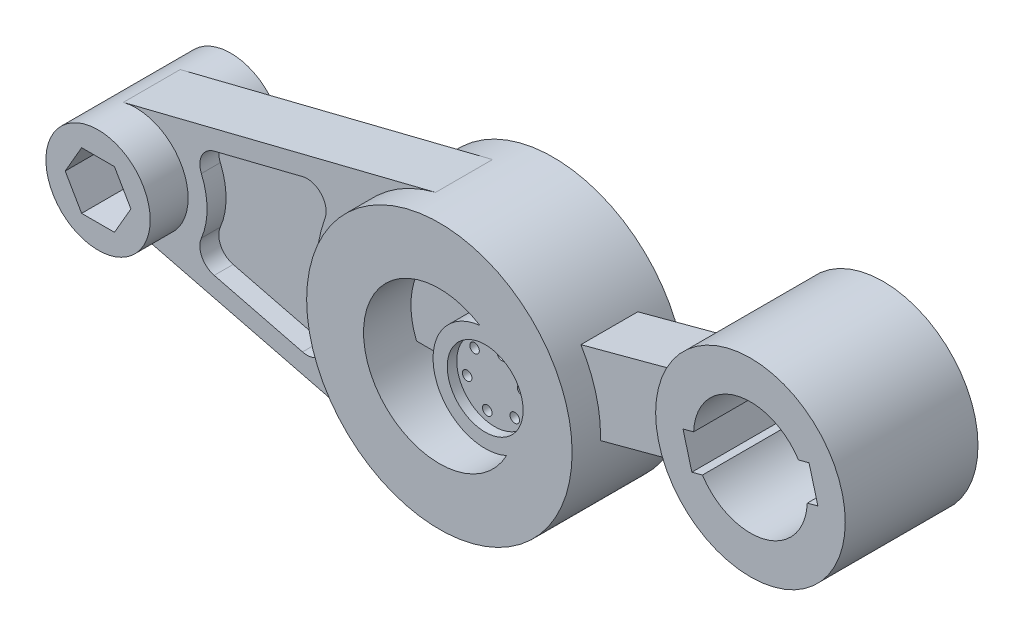
SolidWorks part; units mm, degrees
material "Copper"
ref_plane "Front Plane" through (0, 0, 0) normal (0, 0, 1) x (1, 0, 0)
ref_plane "Top Plane" through (0, 0, 0) normal (0, 1, 0) x (1, 0, 0)
ref_plane "Right Plane" through (0, 0, 0) normal (1, 0, 0) x (0, 0, -1)
ref_plane "CENTRE_Plane" through (175, 0, 0) normal (1, 0, 0) x (0, 0, -1)
ref_axis "CENTRE_Plane_Axis" through (175, 0, 33) along (0, 0, -1)
ref_plane "CENTRE_RIGHT_Plane" through (163.2772, 43.75, 0) normal (0.9659, 0.2588, 0) x (0, 0, -1)
ref_plane "RIGHT_Plane" through (332.3142, 89.0433, 0) normal (0.9659, 0.2588, 0) x (0, 0, -1)
sketch "Sketch1" plane through (0, 0, 0) normal (0, 0, 1) x (1, 0, 0)
  line L0 (-6.6786, 26.6767) -> (158, 67.9043)
  line L1 (-6.6786, -26.6767) -> (158, -67.9043)
  arc A0 (-6.6786, 26.6767) -> (-6.6786, -26.6767) centre (0, 0) ccw
  arc A1 (158, -67.9043) -> (158, 67.9043) centre (175, 0) ccw
  dimension "D1" = 55
  dimension "D2" = 140
extrude "LEFT_ARM" add sketch "Sketch1" along normal mid plane 30
sketch "Sketch2" plane through (0, 0, 0) normal (0, 0, 1) x (1, 0, 0)
  circle A0 centre (0, 0) radius 27.5
  dimension "D1" = 55
extrude "LEFT_Boss" add sketch "Sketch2" along normal mid plane 70
sketch "Sketch4" plane through (0, 0, 35) normal (0, 0, 1) x (1, 0, 0)
  line L0 (33, 0) -> (-33, 0) construction
  line L1 (17.3205, 0) -> (8.6603, 15)
  line L2 (8.6603, 15) -> (-8.6603, 15)
  line L3 (-8.6603, 15) -> (-17.3205, 0)
  line L4 (-17.3205, 0) -> (-8.6603, -15)
  line L5 (-8.6603, -15) -> (8.6603, -15)
  line L6 (8.6603, -15) -> (17.3205, 0)
  circle A0 centre (0, 0) radius 15 construction
  dimension "D1" = 30
extrude "LEFT_Hex" cut sketch "Sketch4" against normal through all both and the other way through all
sketch "Sketch3" plane through (0, 0, 0) normal (0, 0, 1) x (1, 0, 0)
  circle A0 centre (175, 0) radius 70
  dimension "D1" = 140
extrude "CENTRE_Boss" add sketch "Sketch3" along normal mid plane 60
sketch "Sketch5" plane through (163.2772, 43.75, 0) normal (0.9659, 0.2588, 0) x (0, 0, -1)
  line L0 (-33, -45.2933) -> (33, -45.2933) construction
  line L1 (-15, -65.2933) -> (15, -65.2933)
  line L2 (-15, -65.2933) -> (-15, -25.2933)
  line L3 (-15, -25.2933) -> (15, -25.2933)
  line L4 (15, -65.2933) -> (15, -25.2933)
  line L5 (-15, -65.2933) -> (15, -25.2933) construction
  line L6 (-15, -25.2933) -> (15, -65.2933) construction
  line L7 (0, 55) -> (0, -55) construction
  point P0 (0, -45.2933)
  dimension "D1" = 30
  dimension "D2" = 40
extrude "RIGHT_ARM" add sketch "Sketch5" along normal up to surface (175 mm away) up to plane "RIGHT_Plane"
sketch "RIGHT_ARM_CL" plane through (0, 0, 0) normal (0, 0, 1) x (1, 0, 0)
  line L0 (175, 0) -> (344.037, 45.2933) construction
  line L1 (347.6206, 31.9192) -> (317.0079, 146.1675) construction
sketch "Sketch7" plane through (0, 0, 0) normal (0, 0, 1) x (1, 0, 0)
  circle A0 centre (344.037, 45.2933) radius 50
  dimension "D1" = 100
extrude "RIGHT_Boss" add sketch "Sketch7" along normal mid plane 70
sketch "Sketch8" plane through (0, 0, 35) normal (0, 0, 1) x (1, 0, 0)
  circle A0 centre (344.037, 45.2933) radius 30
  dimension "D1" = 60
extrude "RIGHT_Boss_Hole" cut sketch "Sketch8" against normal through all
sketch "Sketch9" plane through (0, 0, 30) normal (0, 0, 1) x (1, 0, 0)
  circle A0 centre (175, 0) radius 40
  dimension "D1" = 80
extrude "CENTRE_Hole" cut sketch "Sketch9" against normal through all
sketch "Sketch10" plane through (0, 0, 0) normal (0, 0, 1) x (1, 0, 0)
  line L0 (175, 0) -> (344.037, 45.2933) construction
  line L1 (178.9358, -14.6885) -> (147.6187, 102.1885) construction
  circle A0 centre (199.1481, 6.4705) radius 27.5
  dimension "D1" = 55
  dimension "D2" = 25
extrude "CENTRE_Blob" add sketch "Sketch10" along normal mid plane 60
sketch "Sketch11" plane through (175, 0, 0) normal (1, 0, 0) x (0, 0, -1)
  line L1 (-5, -15) -> (5, -15)
  line L2 (-5, -15) -> (-5, 15)
  line L3 (-5, 15) -> (5, 15)
  line L4 (5, -15) -> (5, 15)
  line L5 (-5, -15) -> (5, 15) construction
  line L6 (-5, 15) -> (5, -15) construction
  point P0 (0, 0)
  dimension "D1" = 10
  dimension "D2" = 30
extrude "CENTRE_Beam" add sketch "Sketch11" along normal up to next and the other way up to next
sketch "Sketch12" plane through (0, 0, 30) normal (0, 0, 1) x (1, 0, 0)
  circle A0 centre (199.1481, 6.4705) radius 20
  dimension "D1" = 40
extrude "Cut-Extrude4" cut sketch "Sketch12" against normal blind 5
hole_wizard "M6x1.0 Tapped Hole1" positions "Sketch13" profile "Sketch14" tap size "M6x1.0" standard "ANSI Metric" end condition up to next
sketch "Sketch13" plane through (0, 0, 25) normal (0, 0, 1) x (1, 0, 0)
  line L0 (175, 0) -> (344.037, 45.2933) construction
  circle A0 centre (199.1481, 6.4705) radius 20 construction
  point P0 (184.6593, 2.5882)
  dimension "D1" = 15
sketch "Sketch14" plane through (184.6593, 2.5882, 25) normal (1, 0, 0) x (0, -1, 0)
  line L0 (0, 0) -> (0, 55)
  line L1 (0, 55) -> (2.5, 55)
  line L2 (2.5, 55) -> (2.5, 0)
  line L5 (2.5, 0) -> (0, 0)
  line L11 (0, -6.35) -> (0, 107.95) construction
  dimension "Thru Tap Drill Dia." = 5
  dimension "Thru Tap Drill Depth" = 55
cosmetic thread "Hole Thread1" parameters "D2"=6
pattern_circular "CirPattern1" count 6 over 360 about axis through (199.1481, 6.4705, 25) along (0, 0, 1) of "M6x1.0 Tapped Hole1"
cosmetic thread "Hole Thread2" parameters "D2"=6
cosmetic thread "Hole Thread3" parameters "D2"=6
cosmetic thread "Hole Thread4" parameters "D2"=6
cosmetic thread "Hole Thread5" parameters "D2"=6
cosmetic thread "Hole Thread6" parameters "D2"=6
cosmetic thread "Hole Thread7" parameters "D2"=6
cosmetic thread "Hole Thread8" parameters "D2"=6
mirror "Mirror1" about plane through (0, 0, 0) normal (0, 0, 1) of "Cut-Extrude4"
sketch "Sketch15" plane through (0, 0, 15) normal (0, 0, 1) x (1, 0, 0)
  line L24 (109.0977, 45.3529) -> (-4.25, 16.9761)
  line L25 (-4.25, -16.9761) -> (109.0977, -45.3529)
  line L26 (109.0977, 45.3529) -> (27.9233, 25.0307)
  line L27 (27.9233, -25.0307) -> (109.0977, -45.3529)
  arc A12 (109.0977, 45.3529) -> (109.0977, -45.3529) centre (175, 0) ccw
  arc A13 (109.0977, 45.3529) -> (109.0977, -45.3529) centre (175, 0) ccw
  arc A23 (-9.1071, -36.3773) -> (-9.1071, 36.3773) centre (0, 0) ccw
  arc A24 (27.9233, -25.0307) -> (27.9233, 25.0307) centre (0, 0) ccw
  dimension "D1" = 10
  dimension "D2" = 10
extrude "Cut_OUT" cut sketch "Sketch15" against normal blind 10
fillet "Fillet1" radius 10 4 edges at (109.0977, 45.3529, 10) (109.0977, -45.3529, 10) (27.9233, -25.0307, 10) (27.9233, 25.0307, 10)
mirror "Mirror2" about plane through (0, 0, 0) normal (0, 0, 1) of "Fillet1", "Cut_OUT"
sketch "Sketch16" plane through (0, 0, 0) normal (0, 0, 1) x (1, 0, 0)
  line L0 (346.3664, 36.6) -> (341.7076, 53.9867)
  line L1 (347.6206, 31.9192) -> (317.0079, 146.1675) construction
  line L2 (341.7076, 53.9867) -> (308.4798, 45.0833)
  line L3 (308.4798, 45.0833) -> (313.1385, 27.6966)
  line L4 (313.1385, 27.6966) -> (346.3664, 36.6)
  circle A0 centre (344.037, 45.2933) radius 30 construction
  point P4 (344.037, 45.2933)
  dimension "D1" = 18
  dimension "D2" = 34.4
extrude "KEYWAY" cut sketch "Sketch16" against normal through all both and the other way through all
mirror "Mirror3" about plane through (332.3142, 89.0433, 0) normal (0.9659, 0.2588, 0) of "KEYWAY"
equation "\"D1@Sketch2\"=\"D1@Sketch1\""
equation "\"D1@Sketch3\"=\"D2@Sketch1\""
equation "\"D2@Sketch16\"=30+4.4"
